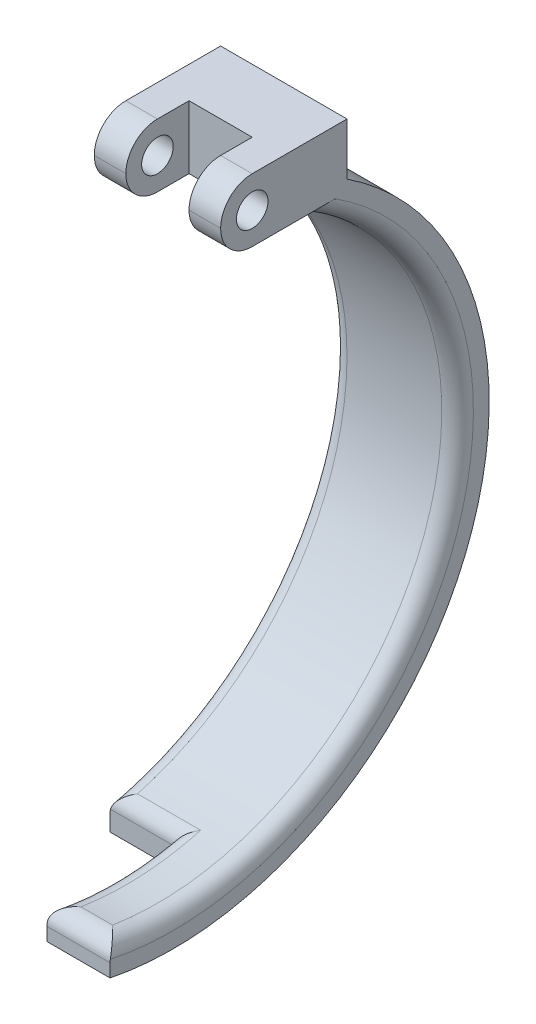
SolidWorks part; units mm, degrees
ref_plane "Front Plane" through (0, 0, 0) normal (0, 0, 1) x (1, 0, 0)
ref_plane "Top Plane" through (0, 0, 0) normal (0, 1, 0) x (1, 0, 0)
ref_plane "Right Plane" through (0, 0, 0) normal (1, 0, 0) x (0, 0, -1)
sketch "Sketch3" plane through (0, 0, 0) normal (1, 0, 0) x (0, 0, -1)
  line L0 (0, 0) -> (7.5, 0) construction
  line L2 (7.5, 0) -> (27.5, 0)
  line L3 (7.5, 0) -> (7.5, 10)
  line L4 (7.5, 10) -> (27.5, 10)
  line L5 (27.5, 0) -> (27.5, 10)
  dimension "D1" = 7.5
  dimension "D2" = 10
  dimension "D3" = 20
extrude "Boss-Extrude2" add sketch "Sketch3" along normal blind 20
sketch "Sketch4" plane through (0, 10, 0) normal (0, 1, 0) x (1, 0, 0)
  line L0 (20, 7.5) -> (0, 7.5) construction
  line L1 (5, 7.5) -> (15, 7.5)
  line L2 (5, 7.5) -> (5, 17.5)
  line L3 (5, 17.5) -> (15, 17.5)
  line L4 (15, 7.5) -> (15, 17.5)
  line L5 (0, 27.5) -> (0, 7.5) construction
  dimension "D1" = 10
  dimension "D2" = 5
  dimension "D3" = 10
extrude "Cut-Extrude2" cut sketch "Sketch4" against normal up to next
sketch "Sketch5" plane through (5, 0, 0) normal (1, 0, 0) x (0, 0, -1)
  circle A0 centre (12.5, 5) radius 2.5
  dimension "D1" = 5
extrude "Cut-Extrude3" cut sketch "Sketch5" against normal through all and the other way through all
sketch "Sketch6" plane through (0, 0, 0) normal (1, 0, 0) x (0, 0, -1)
  line L0 (12.5, 5) -> (0, 5) construction
  line L1 (0, 5) -> (0, -85) construction
  line L2 (7.5, 0) -> (27.5, 0) construction
  line L3 (27.5, 0) -> (27.5, 10) construction
  line L4 (0, -85) -> (0, -90)
  line L5 (27.5, 1.7582) -> (20.6155, 0)
  arc A0 (0, -85) -> (20.6155, 0) centre (0, -40) ccw
  arc A1 (0, -90) -> (27.5, 1.7582) centre (0, -40) ccw
  dimension "D2" = 50
  dimension "D1" = 90
extrude "Boss-Extrude3" add sketch "Sketch6" along normal blind 20
sketch "Sketch7" plane through (20, 0, 0) normal (1, 0, 0) x (0, 0, -1)
  line L0 (0, -85) -> (0, -90)
  line L1 (-10, -83.8748) -> (-10, -88.9898)
  arc A0 (0, -85) -> (-10, -83.8748) centre (0, -40) cw
  arc A1 (0, -90) -> (-10, -88.9898) centre (0, -40) cw
  dimension "D1" = 10
  dimension "D2" = 10
extrude "Boss-Extrude4" add sketch "Sketch7" against normal blind 10
sketch "Sketch8" plane through (0, 0, 0) normal (-1, 0, 0) x (0, 0, 1)
  line L0 (0, -85) -> (0, -90)
  line L1 (-10, -83.8748) -> (-10, -88.9898)
  arc A0 (0, -85) -> (-10, -83.8748) centre (0, -40) cw
  arc A1 (0, -90) -> (-10, -88.9898) centre (0, -40) cw
  dimension "D1" = 10
  dimension "D2" = 10
extrude "Cut-Extrude4" cut sketch "Sketch8" against normal blind 10
fillet "Fillet1" radius 5 4 edges at (17.5, 0, -7.5) (17.5, 10, -7.5) (2.5, 10, -7.5) (2.5, 0, -7.5)
fillet "Fillet2" radius 2.5 5 edges at (15, -83.8748, 10) (5, -83.8748, -10) (10, -85, 0) (20, -55.4299, -42.272) (0, -45.6503, -44.6439)
